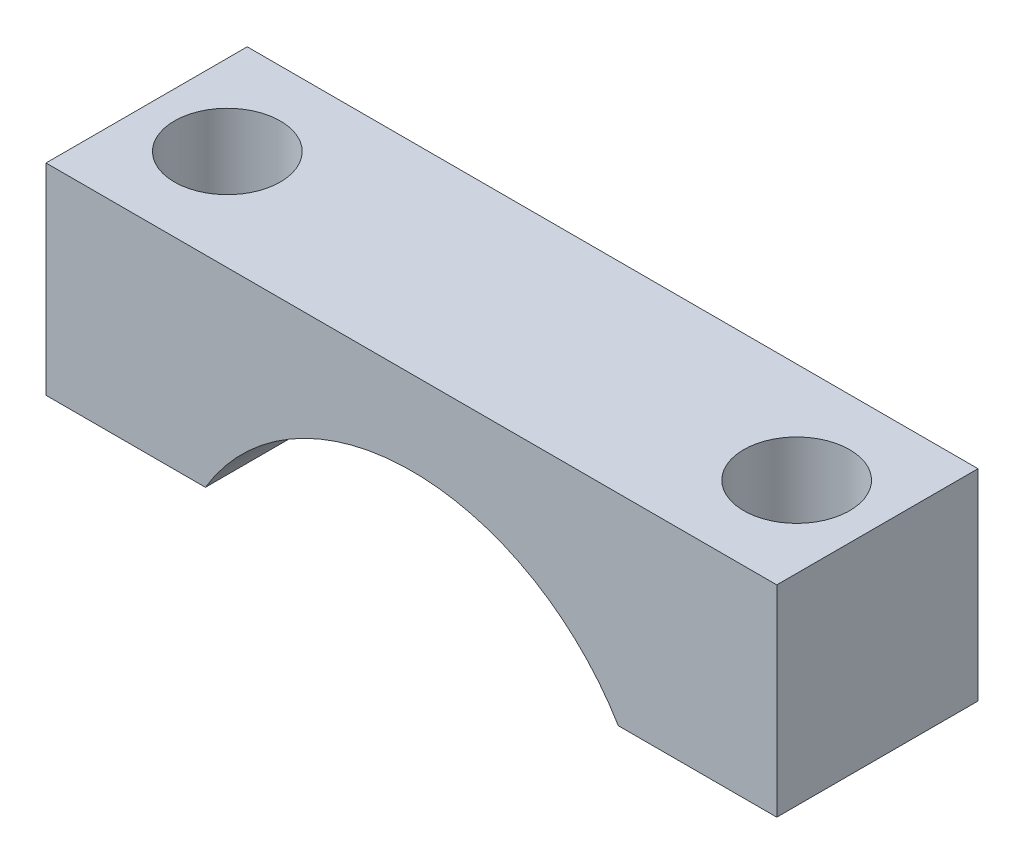
SolidWorks part; units mm, degrees
ref_plane "Front Plane" through (0, 0, 0) normal (0, 0, 1) x (1, 0, 0)
ref_plane "Top Plane" through (0, 0, 0) normal (0, 1, 0) x (1, 0, 0)
ref_plane "Right Plane" through (0, 0, 0) normal (1, 0, 0) x (0, 0, -1)
sketch "Sketch1" plane through (0, 0, 0) normal (0, 0, 1) x (1, 0, 0)
  line L3 (2476.9918, 1418.7932) -> (2476.9918, 1428.4452)
  line L4 (2476.9918, 1428.4452) -> (2512.0438, 1428.4452)
  line L5 (2512.0438, 1428.4452) -> (2512.0438, 1418.7932)
  line L6 (2476.9918, 1418.7932) -> (2484.6376, 1418.7932)
  line L7 (2512.0438, 1418.7932) -> (2504.4411, 1418.7932)
  arc A2 (2484.6376, 1418.7932) -> (2504.4411, 1418.7932) centre (2494.5394, 1412.8969) cw
extrude "Boss-Extrude1" add sketch "Sketch1" along normal blind 9.652
sketch "Sketch2" plane through (0, 1428.4452, 0) normal (0, 1, 0) x (1, 0, 0)
  line L0 (2476.9918, 0) -> (2476.9918, -9.652) construction
  line L1 (2512.0438, -9.652) -> (2476.9918, -9.652) construction
  line L2 (2476.9918, -9.652) -> (2476.9918, 0) construction
  line L3 (2494.5178, 9.3537) -> (2494.5178, -14.3262) construction
  circle A0 centre (2480.8636, -4.826) radius 2.54
  circle A1 centre (2508.172, -4.826) radius 2.54
  point P2 (2476.9918, -4.826)
extrude "Cut-Extrude1" cut sketch "Sketch2" against normal blind 5.08
